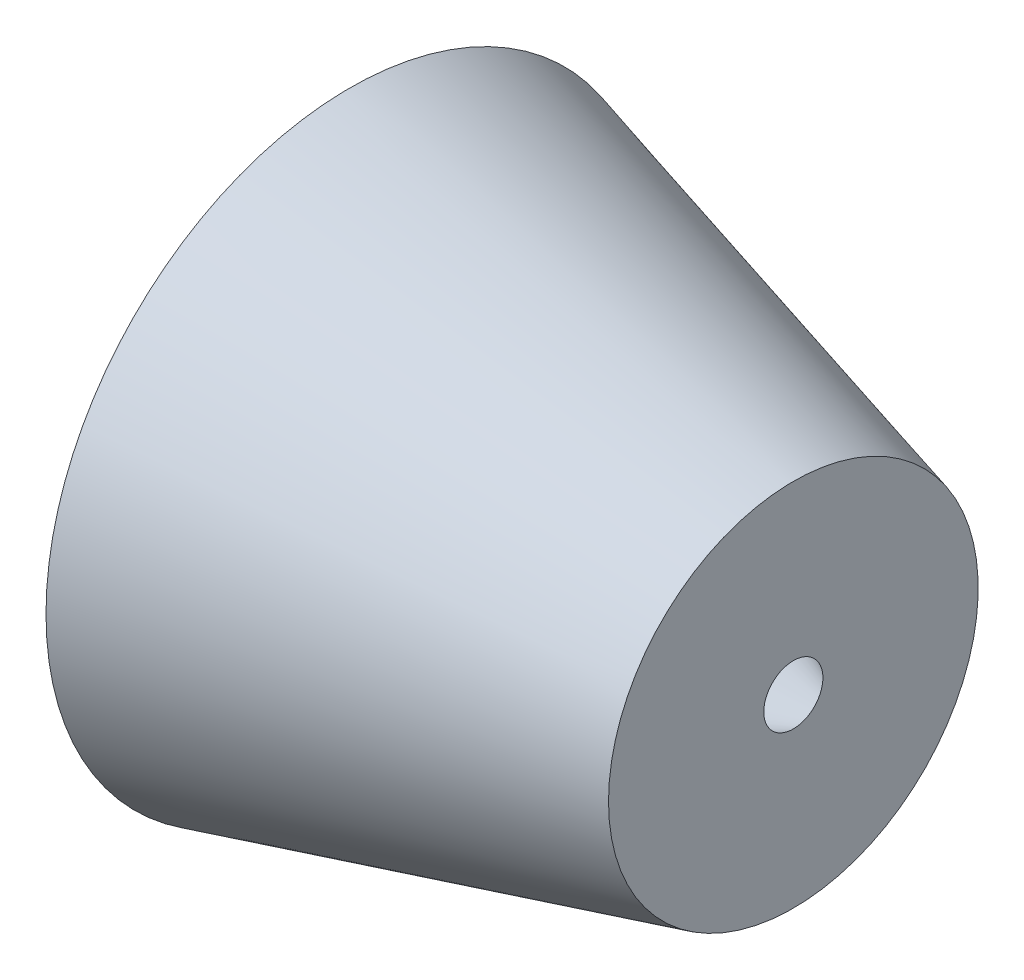
SolidWorks part; units mm, degrees
note: The reader was unsure of these and kept them because the rebuilt part matched: shared geometry of "Sketch4<3>".
ref_plane "Front Plane" through (0, 0, 0) normal (0, 0, 1) x (1, 0, 0)
ref_plane "Top Plane" through (0, 0, 0) normal (0, 1, 0) x (1, 0, 0)
ref_plane "Right Plane" through (0, 0, 0) normal (1, 0, 0) x (0, 0, -1)
sketch "Sketch4" plane through (0, 0, 0) normal (-1, 0, 0) x (0, 0, 1)
  circle A0 centre (0, 0) radius 12.5
  circle A1 centre (0, 0) radius 2
extrude "Boss-Extrude5" add sketch "Sketch4" along normal blind 30 draft 15 separate body contours A0 draft outward yes
extrude "Cut-Extrude2" cut sketch "Sketch4<3>" along normal up to surface (30 mm away) draft 25 contours A1
sketch "Sketch4<3>" plane through (0, 0, 0) normal (-1, 0, 0) x (0, 0, 1) same geometry as "Sketch4"
